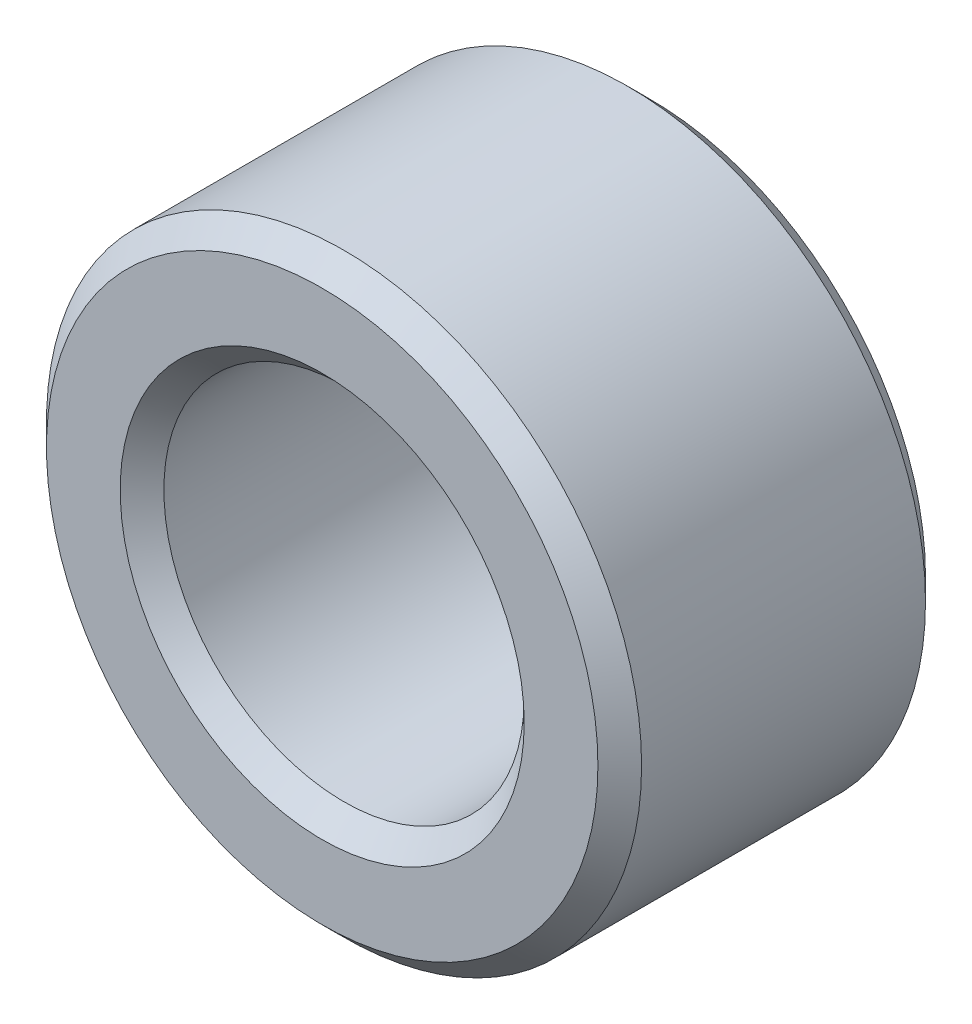
SolidWorks part; units mm, degrees
ref_plane "Front" through (0, 0, 0) normal (0, 0, 1) x (1, 0, 0)
ref_plane "Top" through (0, 0, 0) normal (0, 1, 0) x (1, 0, 0)
ref_plane "Right" through (0, 0, 0) normal (1, 0, 0) x (0, 0, -1)
sketch "Sketch1" plane through (0, 0, 0) normal (0, 0, 1) x (1, 0, 0)
  circle A0 centre (0, 0) radius 1.65
  circle A1 centre (0, 0) radius 2.725
  dimension "D1" = 3.3
  dimension "D2" = 5.45
extrude "Boss-Extrude1" add sketch "Sketch1" along normal blind 3
chamfer "Deburs" distance 0.2 angle 45 4 edges at (1.65, 0, 0) (1.65, 0, 3) (2.725, 0, 0) (2.725, 0, 3)
equation "\"D1@Sketch1\"=\"Hardware Clearance Hole Diameter@Box Assy.Assembly\"+.15mm"
equation "\"D2@Sketch1\"=\"Hardware Head Countersink Diameter@Box Assy.Assembly\"-.15mm"
